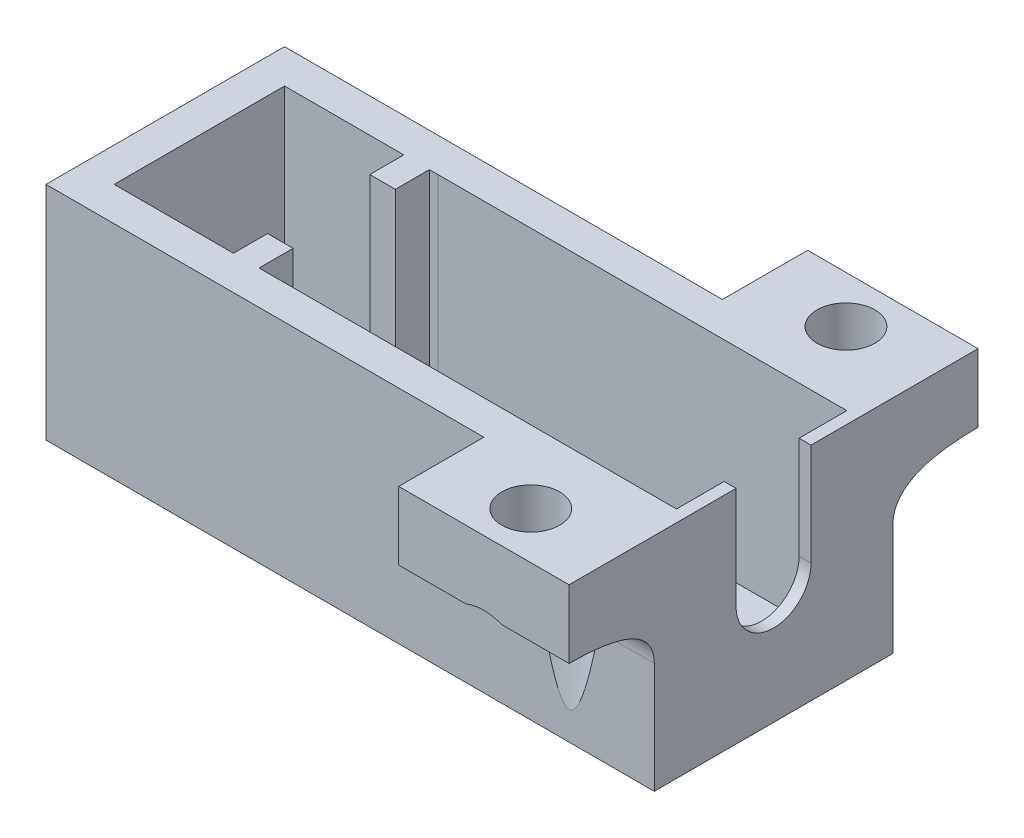
SolidWorks part; units mm, degrees
ref_plane "Front Plane" through (0, 0, 0) normal (0, 0, 1) x (1, 0, 0)
ref_plane "Top Plane" through (0, 0, 0) normal (0, 1, 0) x (1, 0, 0)
ref_plane "Right Plane" through (0, 0, 0) normal (1, 0, 0) x (0, 0, -1)
sketch "Sketch1" plane through (0, 0, 0) normal (0, 1, 0) x (1, 0, 0)
  line L0 (4.8642, 14.8613) -> (4.8642, -1.1387) construction
  line L5 (-7.9858, 14.8613) -> (17.7142, 14.8613)
  line L6 (-7.9858, 14.8613) -> (-7.9858, -1.1387)
  line L7 (-7.9858, -1.1387) -> (17.7142, -1.1387)
  line L8 (17.7142, 14.8613) -> (17.7142, -1.1387)
  line L9 (17.7142, 6.8613) -> (17.0142, 6.8613) construction
  line L10 (17.0142, 6.8613) -> (17.0142, 1.8412) construction
  line L11 (17.0142, 1.8412) -> (17.0142, 11.8412) construction
  line L12 (17.0142, 11.8412) -> (-6.9858, 11.8412) construction
  line L13 (-6.9858, 11.8412) -> (-6.9858, 1.8412) construction
  line L14 (-6.9858, 1.8412) -> (17.0142, 1.8412) construction
  line L16 (-6.9858, 11.8412) -> (17.0142, 11.8412)
  line L17 (-6.9858, 11.8412) -> (-6.9858, 1.8412)
  line L18 (-6.9858, 1.8412) -> (17.0142, 1.8412)
  line L19 (17.0142, 11.8412) -> (17.0142, 1.8412)
extrude "Boss-Extrude5" add sketch "Sketch1" along normal blind 13 contours L6 L5 L8 L7
sketch "Sketch3" plane through (0, 13, 0) normal (0, 1, 0) x (1, 0, 0)
  line L0 (17.7142, 6.8613) -> (17.0154, 6.8613) construction
  line L1 (17.7142, 14.8613) -> (17.7142, -1.1387) construction
  line L2 (17.0154, 6.8613) -> (17.0154, 11.6238) construction
  line L3 (17.0154, 11.6238) -> (17.0154, 1.6238) construction
  line L4 (17.0154, 1.6238) -> (-6.9846, 1.6238) construction
  line L5 (-6.9846, 1.6238) -> (-6.9846, 11.6238) construction
  line L6 (-6.9846, 11.6238) -> (17.0154, 11.6238) construction
  line L8 (-6.9846, 11.6238) -> (17.0154, 11.6238)
  line L9 (-6.9846, 11.6238) -> (-6.9846, 1.6238)
  line L10 (-6.9846, 1.6238) -> (17.0154, 1.6238)
  line L11 (17.0154, 11.6238) -> (17.0154, 1.6238)
extrude "Cut-Extrude1" cut sketch "Sketch3" against normal blind 12
sketch "Sketch6" plane through (-7.9858, 0, 0) normal (-1, 0, 0) x (0, 0, 1)
  line L0 (-6.8613, 13) -> (-6.8613, 0) construction
  line L1 (-14.8613, 13) -> (1.1387, 13) construction
  line L2 (-14.8613, 0) -> (1.1387, 0) construction
  line L3 (-6.8613, 0) -> (-6.8613, 6.5) construction
  line L4 (-6.8613, 13) -> (-9.8613, 13) construction
  line L5 (-9.8613, 13) -> (-9.8613, 1) construction
  line L7 (-9.8613, 13) -> (-3.8613, 13)
  line L8 (-9.8613, 13) -> (-9.8613, 1)
  line L9 (-9.8613, 1) -> (-3.8613, 1)
  line L10 (-3.8613, 13) -> (-3.8613, 1)
extrude "Cut-Extrude6" cut sketch "Sketch6" against normal blind 12
sketch "Sketch12" plane through (0, 0, -14.8613) normal (0, 0, -1) x (-1, 0, 0)
  line L0 (7.9858, 13) -> (7.9858, 0) construction
  line L1 (-17.7142, 13) -> (7.9858, 13)
  line L2 (-17.7142, 13) -> (-17.7142, 0)
  line L3 (-17.7142, 0) -> (7.9858, 0)
  line L4 (7.9858, 13) -> (7.9858, 0)
extrude "Cut-Extrude9" cut sketch "Sketch12" against normal blind 1
sketch "Sketch13" plane through (0, 0, 1.1387) normal (0, 0, 1) x (1, 0, 0)
  line L1 (-7.9858, 13) -> (17.7142, 13)
  line L2 (-7.9858, 13) -> (-7.9858, 0)
  line L3 (-7.9858, 0) -> (17.7142, 0)
  line L4 (17.7142, 13) -> (17.7142, 0)
extrude "Cut-Extrude10" cut sketch "Sketch13" against normal blind 1
sketch "Sketch14" plane through (0, 13, 0) normal (0, 1, 0) x (1, 0, 0)
  line L0 (17.7142, 13.8613) -> (17.7142, -0.1387) construction
  line L1 (-7.9858, 13.8613) -> (17.7142, 13.8613)
  line L2 (-7.9858, 13.8613) -> (-7.9858, 13.6213)
  line L3 (-7.9858, 13.6213) -> (17.7142, 13.6213)
  line L4 (17.7142, 13.8613) -> (17.7142, 13.6213)
extrude "Cut-Extrude11" cut sketch "Sketch14" against normal through all
sketch "Sketch15" plane through (0, 13, 0) normal (0, 1, 0) x (1, 0, 0)
  line L3 (-7.9858, -0.1387) -> (17.7142, -0.1387)
  line L4 (-7.9858, -0.1387) -> (-7.9858, -0.3787)
  line L5 (-7.9858, -0.3787) -> (17.7142, -0.3787)
  line L6 (17.7142, -0.1387) -> (17.7142, -0.3787)
extrude "Boss-Extrude6" add sketch "Sketch15" against normal blind 13
sketch "Sketch17" plane through (17.7142, 0, 0) normal (1, 0, 0) x (0, 0, -1)
  line L0 (13.6213, 13) -> (18.6213, 13)
  line L1 (18.6213, 13) -> (18.6213, 9)
  line L2 (-0.3787, 13) -> (-5.3787, 13)
  line L3 (-5.3787, 13) -> (-5.3787, 9)
  line L4 (18.6213, 9) -> (13.6213, 9) construction
  line L5 (13.6213, 0) -> (13.6213, 13) construction
  line L6 (13.6213, 9) -> (13.6213, 6.5) construction
  line L7 (-5.3787, 9) -> (-0.3787, 9) construction
  line L8 (-0.3787, 0) -> (-0.3787, 13) construction
  line L9 (-0.3787, 9) -> (-0.3787, 6.5) construction
  line L10 (-0.3787, 13) -> (-0.3787, 6.5)
  line L11 (13.6213, 13) -> (13.6213, 6.5)
  spline S0 degree 2 poles (18.6213, 9) (13.6213, 9) (13.6213, 6.5) knots 0 0 0 1 1 1
  spline S1 degree 2 poles (-5.3787, 9) (-0.3787, 9) (-0.3787, 6.5) knots 0 0 0 1 1 1
extrude "Boss-Extrude8" add sketch "Sketch17" against normal blind 10
sketch "Sketch22" plane through (0, 13, 0) normal (0, 1, 0) x (1, 0, 0)
  line L1 (-7.9858, -0.3787) -> (-17.9858, -0.3787)
  line L2 (-7.9858, -0.3787) -> (-7.9858, 13.6213)
  line L3 (-7.9858, 13.6213) -> (-17.9858, 13.6213)
  line L4 (-17.9858, -0.3787) -> (-17.9858, 13.6213)
extrude "Boss-Extrude11" add sketch "Sketch22" against normal blind 13
sketch "Sketch25" plane through (0, 13, 0) normal (0, 1, 0) x (1, 0, 0)
  line L0 (-17.9858, 13.6213) -> (-17.9858, 11.6213) construction
  line L1 (-17.9858, 13.6213) -> (-17.9858, -0.3787) construction
  line L2 (-17.9858, 11.6213) -> (-17.9858, 1.6213) construction
  line L3 (-17.9858, 11.6213) -> (-15.9858, 11.6213) construction
  line L5 (-15.9858, 11.6213) -> (-7.9858, 11.6213)
  line L6 (-15.9858, 11.6213) -> (-15.9858, 1.6213)
  line L7 (-15.9858, 1.6213) -> (-7.9858, 1.6213)
  line L8 (-7.9858, 11.6213) -> (-7.9858, 1.6213)
extrude "Cut-Extrude17" cut sketch "Sketch25" against normal blind 12
sketch "Sketch26" plane through (0, 13, 0) normal (0, 1, 0) x (1, 0, 0)
  line L5 (-6.9846, 1.6238) -> (-7.4846, 1.6238) construction
  line L6 (-6.9846, 11.6238) -> (-7.4846, 11.6238) construction
  line L7 (-7.4846, 1.6238) -> (-8.9846, 1.6238)
  line L8 (-7.4846, 1.6238) -> (-7.4846, 3.6238)
  line L9 (-7.4846, 3.6238) -> (-8.9846, 3.6238)
  line L10 (-8.9846, 1.6238) -> (-8.9846, 3.6238)
  line L12 (-7.4846, 11.6238) -> (-8.9846, 11.6238)
  line L13 (-7.4846, 11.6238) -> (-7.4846, 9.6238)
  line L14 (-7.4846, 9.6238) -> (-8.9846, 9.6238)
  line L15 (-8.9846, 11.6238) -> (-8.9846, 9.6238)
extrude "Boss-Extrude12" add sketch "Sketch26" against normal blind 13
sketch "Sketch27" plane through (0, 13, 0) normal (0, 1, 0) x (1, 0, 0)
  line L1 (-6.9846, 9.8613) -> (-7.4846, 9.8613)
  line L2 (-6.9846, 9.8613) -> (-6.9846, 11.6213)
  line L3 (-6.9846, 11.6213) -> (-7.4846, 11.6213)
  line L4 (-7.4846, 9.8613) -> (-7.4846, 11.6213)
  line L5 (-7.9858, 3.6238) -> (-6.9846, 3.6238)
  line L6 (-7.9858, 3.6238) -> (-7.9858, 3.8613)
  line L7 (-7.9858, 3.8613) -> (-6.9846, 3.8613)
  line L8 (-6.9846, 3.6238) -> (-6.9846, 3.8613)
  line L9 (-6.9846, 1.6238) -> (-7.4852, 1.6238)
  line L10 (-6.9846, 1.6238) -> (-6.9846, 3.6238)
  line L11 (-6.9846, 3.6238) -> (-7.4852, 3.6238)
  line L12 (-7.4852, 1.6238) -> (-7.4852, 3.6238)
  line M9 (-7.4846, 9.8613) -> (-6.9846, 9.8613)
  line M10 (-6.9846, 9.8613) -> (-6.9846, 11.6238)
  line M26 (-6.9846, 1.6238) -> (-6.9846, 3.8613)
extrude "Cut-Extrude18" cut sketch "Sketch27" against normal blind 12 contours L12 L9 L5 M26 | L4 L3 M9 M10 | L5 L8 L7 L6 region at (-7.2346, 13, -10.7413) region at (-7.2349, 13, -2.6238)
sketch "Sketch28" plane through (0, 13, 0) normal (0, 1, 0) x (1, 0, 0)
  line L0 (-8.9846, 3.6238) -> (-8.9846, 1.6238) construction
  line L1 (-8.9846, 1.8186) -> (-7.7072, 1.8186)
  line L2 (-8.9846, 1.8186) -> (-8.9846, 0.9578)
  line L3 (-8.9846, 0.9578) -> (-7.7072, 0.9578)
  line L4 (-7.7072, 1.8186) -> (-7.7072, 0.9578)
extrude "Boss-Extrude13" add sketch "Sketch28" against normal blind 12
sketch "Sketch35" plane through (17.7142, 0, 0) normal (1, 0, 0) x (0, 0, -1)
  line L0 (18.6213, 13) -> (6.6213, 13) construction
  line L2 (18.6213, 13) -> (-5.3787, 13) construction
  line L3 (6.6213, 13) -> (6.6213, 7) construction
  line L4 (4.4214, 7) -> (4.4214, 13)
  line L5 (4.4214, 13) -> (8.8212, 13)
  line L6 (8.8212, 13) -> (8.8212, 7)
  arc A0 (8.8212, 7) -> (4.4214, 7) centre (6.6213, 7) cw
extrude "Cut-Extrude20" cut sketch "Sketch35" against normal blind 12
sketch "Sketch39" plane through (0, 13, 0) normal (0, 1, 0) x (1, 0, 0)
  line L0 (12.7142, 18.6213) -> (12.7142, 15.8713) construction
  line L1 (12.7142, -5.3787) -> (12.7142, -2.6287) construction
  circle A0 centre (12.7142, 15.8713) radius 1.7
  circle A2 centre (12.7142, -2.6287) radius 1.7
  circle A3 centre (12.7142, 15.8713) radius 3.15
  circle A4 centre (12.7142, -2.6287) radius 3.15
extrude "Cut-Extrude21" cut sketch "Sketch39" against normal blind 1.5 draft 45 from offset 2.75 contours A0 | A2 draft outward yes offset against normal yes
extrude "Cut-Extrude22" cut sketch "Sketch39<4>" against normal blind 5 contours A0 | A2
sketch "Sketch39<4>" plane through (0, 13, 0) normal (0, 1, 0) x (1, 0, 0) same geometry as "Sketch39"
extrude "Cut-Extrude23" cut sketch "Sketch39<5>" against normal blind 10 draft 7 from offset 4 contours A4 | A3 offset against normal yes
sketch "Sketch39<5>" plane through (0, 13, 0) normal (0, 1, 0) x (1, 0, 0) same geometry as "Sketch39"
